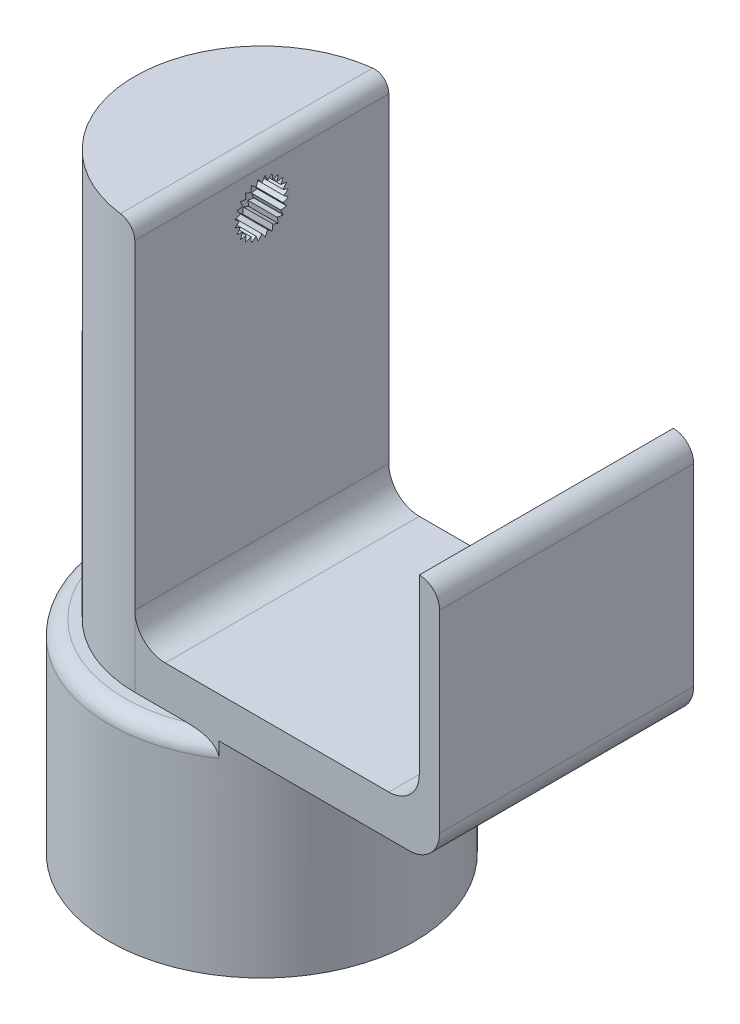
SolidWorks part; units mm, degrees
ref_plane "Front Plane" through (0, 0, 0) normal (0, 0, 1) x (1, 0, 0)
ref_plane "Top Plane" through (0, 0, 0) normal (0, 1, 0) x (1, 0, 0)
ref_plane "Right Plane" through (0, 0, 0) normal (1, 0, 0) x (0, 0, -1)
sketch "Sketch1" plane through (0, 0, 0) normal (0, 1, 0) x (1, 0, 0)
  circle A0 centre (0, 0) radius 15
  dimension "D1" = 30
extrude "Boss-Extrude1" add sketch "Sketch1" along normal blind 20
sketch "Sketch3" plane through (0, 0, 0) normal (0, -1, 0) x (1, 0, 0)
  circle A0 centre (0, 0) radius 2.65
  dimension "D1" = 5.3
extrude "Cut-Extrude1" cut sketch "Sketch3" against normal blind 2.5
sketch "Sketch4" plane through (0, 2.5, 0) normal (0, -1, 0) x (1, 0, 0)
  line L4 (-2.1494, -1.55) -> (2.1494, -1.55)
  line L5 (-2.1494, -1.55) -> (-2.1494, 1.55) construction
  line L6 (-2.1494, 1.55) -> (2.1494, 1.55)
  line L7 (2.1494, -1.55) -> (2.1494, 1.55) construction
  line L8 (-2.1494, -1.55) -> (2.1494, 1.55) construction
  line L9 (-2.1494, 1.55) -> (2.1494, -1.55) construction
  arc A3 (-2.1494, 1.55) -> (-2.1494, -1.55) centre (0, 0) ccw
  arc A4 (2.1494, 1.55) -> (-2.1494, 1.55) centre (0, 0) ccw construction
  arc A5 (-2.1494, -1.55) -> (2.1494, -1.55) centre (0, 0) ccw construction
  arc A6 (2.1494, -1.55) -> (2.1494, 1.55) centre (0, 0) ccw
  point P0 (0, 0)
  dimension "D2" = 5.3
  dimension "D1" = 3.1
extrude "Cut-Extrude2" cut sketch "Sketch4" against normal blind 6
sketch "Sketch5" plane through (0, 20, 0) normal (0, 1, 0) x (1, 0, 0)
  line L0 (0, 12.5) -> (0, -12.5)
  arc A0 (0, 12.5) -> (0, -12.5) centre (0, 0) ccw
  dimension "D1" = 25
extrude "Boss-Extrude2" add sketch "Sketch5" along normal blind 40
sketch "Sketch6" plane through (0, 0, 0) normal (1, 0, 0) x (0, 0, -1)
  line L2 (-12.5, 60) -> (12.5, 60) construction
  line L3 (-12.5, 55) -> (12.5, 55) construction
  line L4 (-12.5, 60) -> (-12.5, 20) construction
  line L5 (12.5, 60) -> (12.5, 20) construction
  dimension "D1" = 5
sketch "Sketch13" plane through (0, 0, 0) normal (1, 0, 0) x (0, 0, -1)
  line L72 (2.6281, 54.66) -> (2.17, 55)
  line L73 (2.17, 55) -> (2.6271, 55.3473)
  line L74 (2.6271, 55.3473) -> (2.6265, 55.3518)
  line L75 (2.6265, 55.3518) -> (2.0961, 55.5616)
  line L76 (2.0961, 55.5616) -> (2.4477, 56.0154)
  line L77 (2.4477, 56.0154) -> (2.446, 56.0196)
  line L78 (2.446, 56.0196) -> (1.8793, 56.085)
  line L79 (1.8793, 56.085) -> (2.1015, 56.6143)
  line L80 (2.1015, 56.6143) -> (2.0988, 56.6179)
  line L81 (2.0988, 56.6179) -> (1.5344, 56.5344)
  line L82 (1.5344, 56.5344) -> (1.6121, 57.1032)
  line L83 (1.6121, 57.1032) -> (1.6085, 57.106)
  line L84 (1.6085, 57.106) -> (1.085, 56.8793)
  line L85 (1.085, 56.8793) -> (1.0128, 57.4488)
  line L86 (1.0128, 57.4488) -> (1.0086, 57.4505)
  line L87 (1.0086, 57.4505) -> (0.5616, 57.0961)
  line L88 (0.5616, 57.0961) -> (0.3445, 57.6275)
  line L89 (0.3445, 57.6275) -> (0.34, 57.6281)
  line L90 (0.34, 57.6281) -> (0, 57.17)
  line L91 (0, 57.17) -> (-0.3473, 57.6271)
  line L92 (-0.3473, 57.6271) -> (-0.3518, 57.6265)
  line L93 (-0.3518, 57.6265) -> (-0.5616, 57.0961)
  line L94 (-0.5616, 57.0961) -> (-1.0154, 57.4477)
  line L95 (-1.0154, 57.4477) -> (-1.0196, 57.446)
  line L96 (-1.0196, 57.446) -> (-1.085, 56.8793)
  line L97 (-1.085, 56.8793) -> (-1.6143, 57.1015)
  line L98 (-1.6143, 57.1015) -> (-1.6179, 57.0988)
  line L99 (-1.6179, 57.0988) -> (-1.5344, 56.5344)
  line L100 (-1.5344, 56.5344) -> (-2.1032, 56.6121)
  line L101 (-2.1032, 56.6121) -> (-2.106, 56.6085)
  line L102 (-2.106, 56.6085) -> (-1.8793, 56.085)
  line L103 (-1.8793, 56.085) -> (-2.4488, 56.0128)
  line L104 (-2.4488, 56.0128) -> (-2.4505, 56.0086)
  line L105 (-2.4505, 56.0086) -> (-2.0961, 55.5616)
  line L106 (-2.0961, 55.5616) -> (-2.6275, 55.3445)
  line L107 (-2.6275, 55.3445) -> (-2.6281, 55.34)
  line L108 (-2.6281, 55.34) -> (-2.17, 55)
  line L109 (-2.17, 55) -> (-2.6271, 54.6527)
  line L110 (-2.6271, 54.6527) -> (-2.6265, 54.6482)
  line L111 (-2.6265, 54.6482) -> (-2.0961, 54.4384)
  line L112 (-2.0961, 54.4384) -> (-2.4477, 53.9846)
  line L113 (-2.4477, 53.9846) -> (-2.446, 53.9804)
  line L114 (-2.446, 53.9804) -> (-1.8793, 53.915)
  line L115 (-1.8793, 53.915) -> (-2.1015, 53.3857)
  line L116 (-2.1015, 53.3857) -> (-2.0988, 53.3821)
  line L117 (-2.0988, 53.3821) -> (-1.5344, 53.4656)
  line L118 (-1.5344, 53.4656) -> (-1.6121, 52.8968)
  line L119 (-1.6121, 52.8968) -> (-1.6085, 52.894)
  line L120 (-1.6085, 52.894) -> (-1.085, 53.1207)
  line L121 (-1.085, 53.1207) -> (-1.0128, 52.5512)
  line L122 (-1.0128, 52.5512) -> (-1.0086, 52.5495)
  line L123 (-1.0086, 52.5495) -> (-0.5616, 52.9039)
  line L124 (-0.5616, 52.9039) -> (-0.3445, 52.3725)
  line L125 (-0.3445, 52.3725) -> (-0.34, 52.3719)
  line L126 (-0.34, 52.3719) -> (0, 52.83)
  line L127 (0, 52.83) -> (0.3473, 52.3729)
  line L128 (0.3473, 52.3729) -> (0.3518, 52.3735)
  line L129 (0.3518, 52.3735) -> (0.5616, 52.9039)
  line L130 (0.5616, 52.9039) -> (1.0154, 52.5523)
  line L131 (1.0154, 52.5523) -> (1.0196, 52.554)
  line L132 (1.0196, 52.554) -> (1.085, 53.1207)
  line L133 (1.085, 53.1207) -> (1.6143, 52.8985)
  line L134 (1.6143, 52.8985) -> (1.6179, 52.9012)
  line L135 (1.6179, 52.9012) -> (1.5344, 53.4656)
  line L136 (1.5344, 53.4656) -> (2.1032, 53.3879)
  line L137 (2.1032, 53.3879) -> (2.106, 53.3915)
  line L138 (2.106, 53.3915) -> (1.8793, 53.915)
  line L139 (1.8793, 53.915) -> (2.4488, 53.9872)
  line L140 (2.4488, 53.9872) -> (2.4505, 53.9914)
  line L141 (2.4505, 53.9914) -> (2.0961, 54.4384)
  line L142 (2.0961, 54.4384) -> (2.6275, 54.6555)
  line L143 (2.6275, 54.6555) -> (2.6281, 54.66)
  line L144 (2.6281, 54.66) -> (2.17, 55)
  line L145 (2.17, 55) -> (2.6271, 55.3473)
  line L146 (2.6271, 55.3473) -> (2.6265, 55.3518)
  line L147 (2.6265, 55.3518) -> (2.0961, 55.5616)
  line L148 (2.0961, 55.5616) -> (2.4477, 56.0154)
  line L149 (2.4477, 56.0154) -> (2.446, 56.0196)
  line L150 (2.446, 56.0196) -> (1.8793, 56.085)
  line L151 (1.8793, 56.085) -> (2.1015, 56.6143)
  line L152 (2.1015, 56.6143) -> (2.0988, 56.6179)
  line L153 (2.0988, 56.6179) -> (1.5344, 56.5344)
  line L154 (1.5344, 56.5344) -> (1.6121, 57.1032)
  line L155 (1.6121, 57.1032) -> (1.6085, 57.106)
  line L156 (1.6085, 57.106) -> (1.085, 56.8793)
  line L157 (1.085, 56.8793) -> (1.0128, 57.4488)
  line L158 (1.0128, 57.4488) -> (1.0086, 57.4505)
  line L159 (1.0086, 57.4505) -> (0.5616, 57.0961)
  line L160 (0.5616, 57.0961) -> (0.3445, 57.6275)
  line L161 (0.3445, 57.6275) -> (0.34, 57.6281)
  line L162 (0.34, 57.6281) -> (0, 57.17)
  line L163 (0, 57.17) -> (-0.3473, 57.6271)
  line L164 (-0.3473, 57.6271) -> (-0.3518, 57.6265)
  line L165 (-0.3518, 57.6265) -> (-0.5616, 57.0961)
  line L166 (-0.5616, 57.0961) -> (-1.0154, 57.4477)
  line L167 (-1.0154, 57.4477) -> (-1.0196, 57.446)
  line L168 (-1.0196, 57.446) -> (-1.085, 56.8793)
  line L169 (-1.085, 56.8793) -> (-1.6143, 57.1015)
  line L170 (-1.6143, 57.1015) -> (-1.6179, 57.0988)
  line L171 (-1.6179, 57.0988) -> (-1.5344, 56.5344)
  line L172 (-1.5344, 56.5344) -> (-2.1032, 56.6121)
  line L173 (-2.1032, 56.6121) -> (-2.106, 56.6085)
  line L174 (-2.106, 56.6085) -> (-1.8793, 56.085)
  line L175 (-1.8793, 56.085) -> (-2.4488, 56.0128)
  line L176 (-2.4488, 56.0128) -> (-2.4505, 56.0086)
  line L177 (-2.4505, 56.0086) -> (-2.0961, 55.5616)
  line L178 (-2.0961, 55.5616) -> (-2.6275, 55.3445)
  line L179 (-2.6275, 55.3445) -> (-2.6281, 55.34)
  line L180 (-2.6281, 55.34) -> (-2.17, 55)
  line L181 (-2.17, 55) -> (-2.6271, 54.6527)
  line L182 (-2.6271, 54.6527) -> (-2.6265, 54.6482)
  line L183 (-2.6265, 54.6482) -> (-2.0961, 54.4384)
  line L184 (-2.0961, 54.4384) -> (-2.4477, 53.9846)
  line L185 (-2.4477, 53.9846) -> (-2.446, 53.9804)
  line L186 (-2.446, 53.9804) -> (-1.8793, 53.915)
  line L187 (-1.8793, 53.915) -> (-2.1015, 53.3857)
  line L188 (-2.1015, 53.3857) -> (-2.0988, 53.3821)
  line L189 (-2.0988, 53.3821) -> (-1.5344, 53.4656)
  line L190 (-1.5344, 53.4656) -> (-1.6121, 52.8968)
  line L191 (-1.6121, 52.8968) -> (-1.6085, 52.894)
  line L192 (-1.6085, 52.894) -> (-1.085, 53.1207)
  line L193 (-1.085, 53.1207) -> (-1.0128, 52.5512)
  line L194 (-1.0128, 52.5512) -> (-1.0086, 52.5495)
  line L195 (-1.0086, 52.5495) -> (-0.5616, 52.9039)
  line L196 (-0.5616, 52.9039) -> (-0.3445, 52.3725)
  line L197 (-0.3445, 52.3725) -> (-0.34, 52.3719)
  line L198 (-0.34, 52.3719) -> (0, 52.83)
  line L199 (0, 52.83) -> (0.3473, 52.3729)
  line L200 (0.3473, 52.3729) -> (0.3518, 52.3735)
  line L201 (0.3518, 52.3735) -> (0.5616, 52.9039)
  line L202 (0.5616, 52.9039) -> (1.0154, 52.5523)
  line L203 (1.0154, 52.5523) -> (1.0196, 52.554)
  line L204 (1.0196, 52.554) -> (1.085, 53.1207)
  line L205 (1.085, 53.1207) -> (1.6143, 52.8985)
  line L206 (1.6143, 52.8985) -> (1.6179, 52.9012)
  line L207 (1.6179, 52.9012) -> (1.5344, 53.4656)
  line L208 (1.5344, 53.4656) -> (2.1032, 53.3879)
  line L209 (2.1032, 53.3879) -> (2.106, 53.3915)
  line L210 (2.106, 53.3915) -> (1.8793, 53.915)
  line L211 (1.8793, 53.915) -> (2.4488, 53.9872)
  line L212 (2.4488, 53.9872) -> (2.4505, 53.9914)
  line L213 (2.4505, 53.9914) -> (2.0961, 54.4384)
  line L214 (2.0961, 54.4384) -> (2.6275, 54.6555)
  line L215 (2.6275, 54.6555) -> (2.6281, 54.66)
  dimension "D1" = 0
extrude "Cut-Extrude4" cut sketch "Sketch13" against normal blind 2.9
sketch "Sketch14" plane through (-2.9, 0, 0) normal (1, 0, 0) x (0, 0, -1)
  line L0 (-12.5, 55) -> (12.5, 55) construction
  circle A0 centre (0, 55) radius 1.25
  dimension "D1" = 2.5
extrude "Cut-Extrude5" cut sketch "Sketch14" against normal blind 1.5
sketch "Sketch15" plane through (-2.9, 0, 0) normal (1, 0, 0) x (0, 0, -1)
  line L0 (-12.5, 55) -> (12.5, 55) construction
  circle A0 centre (0, 55) radius 3
  dimension "D1" = 6
extrude "Cut-Extrude6" cut sketch "Sketch15" against normal through all from offset 1.5 offset against normal yes
sketch "Sketch16" plane through (0, 0, 0) normal (1, 0, 0) x (0, 0, -1)
  line L0 (12.5, 60) -> (12.5, 20) construction
  line L1 (-12.5, 20) -> (12.5, 20)
  line L2 (-12.5, 20) -> (-12.5, 24)
  line L3 (-12.5, 24) -> (12.5, 24)
  line L4 (12.5, 20) -> (12.5, 24)
  dimension "D1" = 4
extrude "Boss-Extrude3" add sketch "Sketch16" along normal blind 30
sketch "Sketch17" plane through (0, 24, 0) normal (0, 1, 0) x (1, 0, 0)
  line L0 (30, -12.5) -> (0, -12.5) construction
  line L1 (30, 12.5) -> (28, 12.5)
  line L2 (30, 12.5) -> (30, -12.5)
  line L3 (30, -12.5) -> (28, -12.5)
  line L4 (28, 12.5) -> (28, -12.5)
  dimension "D1" = 2
extrude "Boss-Extrude4" add sketch "Sketch17" along normal blind 20
fillet "Fillet1" radius 3 1 edges at (30, 20, 0)
fillet "Fillet2" radius 2 1 edges at (30, 44, 0)
fillet "Fillet3" radius 3 2 edges at (28, 24, 0) (0, 24, 0)
fillet "Fillet4" radius 1.5 1 edges at (0, 60, 0)
fillet "Fillet5" radius 1.5 1 edges at (-15, 20, 0)
